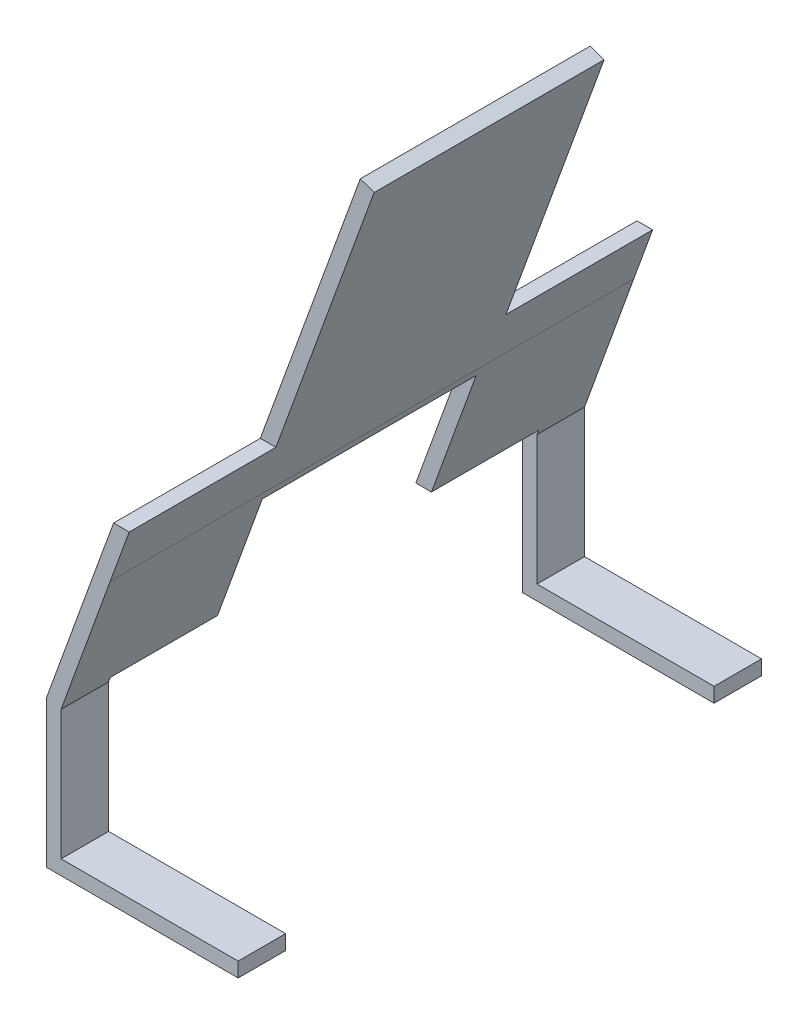
SolidWorks part; units mm, degrees
ref_plane "Front Plane" through (0, 0, 0) normal (0, 0, 1) x (1, 0, 0)
ref_plane "Top Plane" through (0, 0, 0) normal (0, 1, 0) x (1, 0, 0)
ref_plane "Right Plane" through (0, 0, 0) normal (1, 0, 0) x (0, 0, -1)
sketch "Sketch1" plane through (0, 0, 0) normal (0, 0, 1) x (1, 0, 0)
  line L0 (0, 0) -> (0, 3)
  line L1 (0, 3) -> (-36.1925, 3)
  line L2 (-36.1925, 3) -> (-36.1925, 29.4727)
  line L3 (-36.1925, 29.4727) -> (-26.1428, 57.1773)
  line L4 (-26.1428, 57.1773) -> (-2.2019, 122.9543)
  line L5 (-2.2019, 122.9543) -> (-5.021, 123.9804)
  line L6 (-5.021, 123.9804) -> (-28.9624, 58.2019)
  line L7 (-28.9624, 58.2019) -> (-39.1925, 30)
  line L8 (-39.1925, 30) -> (-39.1925, 0)
  line L9 (-39.1925, 0) -> (0, 0)
  line L10 (-26.1428, 57.1773) -> (0.1704, 57.1773) construction
  dimension "D1" = 3
  dimension "D2" = 3
  dimension "D3" = 3
  dimension "D4" = 3
  dimension "D5" = 70
  dimension "D6" = 30
  dimension "D7" = 30
  dimension "D8" = 70
extrude "Boss-Extrude1" add sketch "Sketch1" along normal blind 107
sketch "Sketch2" plane through (0, 0, 0) normal (1, 0, 0) x (0, 0, -1)
  line L0 (-107, 0) -> (0, 0) construction
  line L2 (-97.2882, 0) -> (-97.2882, 30.4293)
  line L3 (-97.2882, 30.4293) -> (-75.3624, 30.4293)
  line L4 (-9.7118, 0) -> (-9.7118, 30.4293)
  line L5 (-31.6376, 30.4293) -> (-9.7118, 30.4293)
  line L6 (-53.5, 123.9804) -> (-53.5, -6.3249) construction
  line L7 (-97.2882, 0) -> (-9.7118, 0)
  line L9 (-75.3624, 30.4293) -> (-75.3624, 55.6503)
  line L10 (-75.3624, 55.6503) -> (-31.6376, 55.6503)
  line L11 (-31.6376, 30.4293) -> (-31.6376, 55.6503)
  line L12 (-107, 123.9804) -> (-77.01, 123.9804)
  line L13 (-107, 123.9804) -> (-107, 67.8172)
  line L14 (-107, 67.8172) -> (-77.01, 67.8172)
  line L15 (-77.01, 123.9804) -> (-77.01, 67.8172)
  line L16 (-107, 123.9804) -> (0, 123.9804) construction
  line L17 (0, 67.8172) -> (-29.99, 67.8172)
  line L18 (-29.99, 123.9804) -> (-29.99, 67.8172)
  line L19 (0, 123.9804) -> (0, 67.8172)
  line L20 (0, 123.9804) -> (-29.99, 123.9804)
  point P0 (-53.5, 0)
  point P7 (-53.5, 30.4293)
extrude "Cut-Extrude1" cut sketch "Sketch2" against normal blind 107 and the other way blind 107
